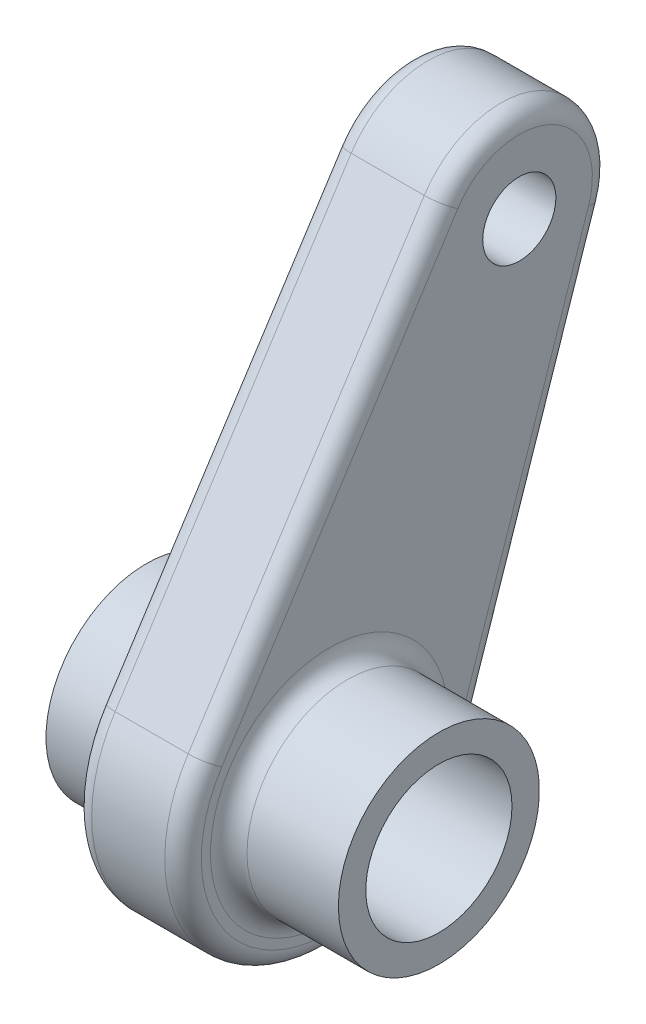
SolidWorks part; units mm, degrees
material "PVC 0.007 Plasticized"
ref_plane "Front Plane" through (0, 0, 0) normal (0, 0, 1) x (1, 0, 0)
ref_plane "Top Plane" through (0, 0, 0) normal (0, 1, 0) x (1, 0, 0)
ref_plane "Right Plane" through (0, 0, 0) normal (1, 0, 0) x (0, 0, -1)
sketch "Sketch1" plane through (0, 0, 0) normal (1, 0, 0) x (0, 0, -1)
  line L0 (0, 0) -> (33.0165, 68.6757) construction
  line L2 (48.0715, 63.6396) -> (24.088, -8.0577)
  line L3 (-21.3367, 13.7807) -> (19.6811, 77.2886)
  circle A0 centre (0, 0) radius 12.7
  circle A1 centre (33.0165, 68.6757) radius 6.35
  circle A2 centre (33.0165, 68.6757) radius 15.875
  arc A4 (-21.3367, 13.7807) -> (24.088, -8.0577) centre (0, 0) ccw
  circle A5 centre (0, 0) radius 17.4625
  point P5 (0, 0)
  point P6 (0, 0)
  dimension "D1" = 76.2
extrude "Boss-Extrude1" add sketch "Sketch1" against normal blind 12.7 contours A0 A5 region at (0, 0, 16.9686)
extrude "Boss-Extrude2" add sketch "Sketch1<3>" along normal blind 19.05 contours A5 A2 L3 A4 L2 | A0 A5 | A2 A1 region at (0, 23.2781, -11.1912) region at (0, 54.7729, -26.3326) region at (0, 0, 16.9686)
sketch "Sketch1<3>" plane through (0, 0, 0) normal (1, 0, 0) x (0, 0, -1) same geometry as "Sketch1"
extrude "Boss-Extrude3" add sketch "Sketch1<4>" along normal blind 38.1 contours A0 A5 region at (0, 0, 16.9686)
sketch "Sketch1<4>" plane through (0, 0, 0) normal (1, 0, 0) x (0, 0, -1) same geometry as "Sketch1"
fillet "Fillet1" radius 3.175 10 edges at (0, 45.5346, 0.8278) (0, 82.9831, -39.8949) (0, 27.791, -36.0798) (19.05, 45.5346, 0.8278) (19.05, 82.9831, -39.8949) (19.05, 27.791, -36.0798) (0, 0, -17.4625) (0, -22.8919, 11.0055) (19.05, -22.8919, 11.0055) (19.05, 0, -17.4625)
